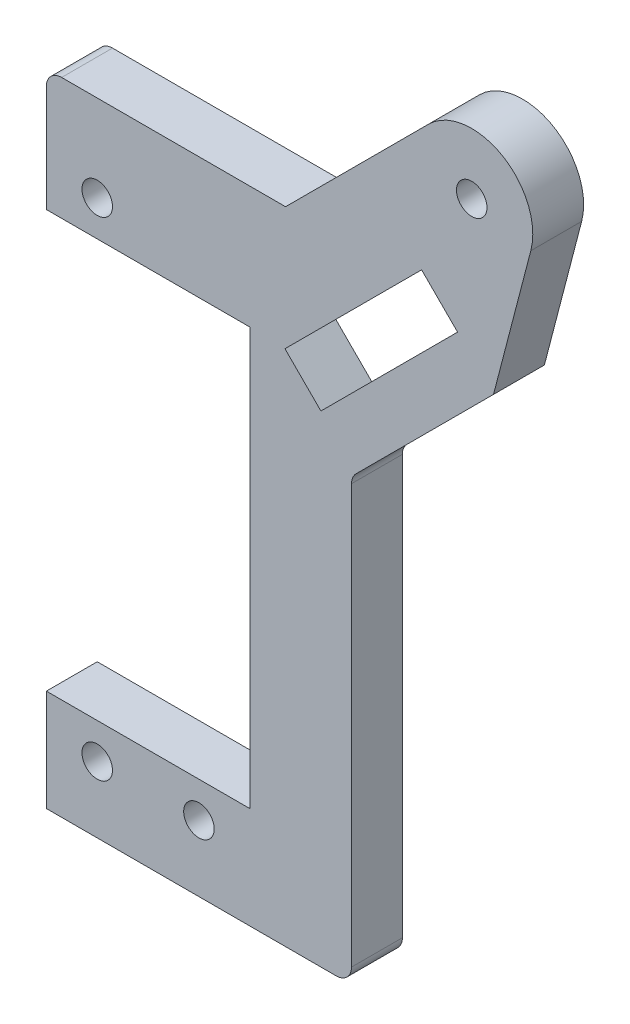
SolidWorks part; units mm, degrees
ref_plane "Plan de face" through (0, 0, 0) normal (0, 0, 1) x (1, 0, 0)
ref_plane "Plan de dessus" through (0, 0, 0) normal (0, 1, 0) x (1, 0, 0)
ref_plane "Plan de droite" through (0, 0, 0) normal (1, 0, 0) x (0, 0, -1)
sketch "Esquisse1" plane through (0, 0, 0) normal (0, 0, 1) x (1, 0, 0)
  line L0 (0, 10) -> (0, 0)
  line L1 (0, 0) -> (30, 0)
  line L2 (10, 10) -> (10, 51) construction
  line L3 (0, 63) -> (23.5147, 63)
  line L4 (36.8905, 64.3141) -> (23.4554, 50.8791)
  line L5 (11, 51) -> (0, 51)
  line L6 (36.8905, 64.3141) -> (40.426, 60.7786)
  line L7 (20, 10) -> (11, 10)
  line L8 (0, 30.5) -> (0, 10)
  line L9 (0, 30.5) -> (20, 30.5) construction
  line L10 (20, 10) -> (20, 51)
  line L11 (20, 51) -> (11, 51)
  line L12 (47.626, 71.307) -> (43.9615, 57.2431)
  line L13 (43.9615, 57.2431) -> (30, 43.2815)
  line L14 (23.4554, 50.8791) -> (26.991, 47.3436)
  line L15 (26.991, 47.3436) -> (40.426, 60.7786)
  line L16 (37.5772, 77.0624) -> (23.5147, 63)
  line L18 (11, 10) -> (0, 10)
  line L24 (30, 43.2815) -> (30, 0)
  line L25 (0, 63) -> (0, 51)
  line L26 (40.426, 60.7786) -> (43.9615, 57.2431) construction
  circle A0 centre (5, 54.5) radius 1.5
  circle A1 centre (15, 54.5) radius 1.5 construction
  circle A2 centre (15, 6.5) radius 1.5
  circle A3 centre (5, 6.5) radius 1.5
  circle A4 centre (41.8198, 72.8198) radius 1.5
  circle A5 centre (41.8198, 72.8198) radius 1.725 construction
  arc A6 (37.5772, 77.0624) -> (47.626, 71.307) centre (41.8198, 72.8198) cw
  dimension "D6" = 20
  dimension "D8" = 5
  dimension "D11" = 3
  dimension "D16" = 10
  dimension "D5" = 3
  dimension "D12" = 19
  dimension "D13" = 6
  dimension "D1" = 41
  dimension "D2" = 12
  dimension "D3" = 3.5
  dimension "D4" = 5
  dimension "D7" = 5
  dimension "D14" = 10
extrude "Boss.-Extru.1" add sketch "Esquisse1" along normal blind 5 contours L3 L25 L1 L4 L14 L15 L18 L8 L5 L11 L10 L7 A0 A2 A3 region at (23.669, 40.2812, 0)
fillet "Congé3" radius 1.5 3 edges at (0, 63, 2.5) (30, 0, 2.5) (30, 43.2815, 2.5)
